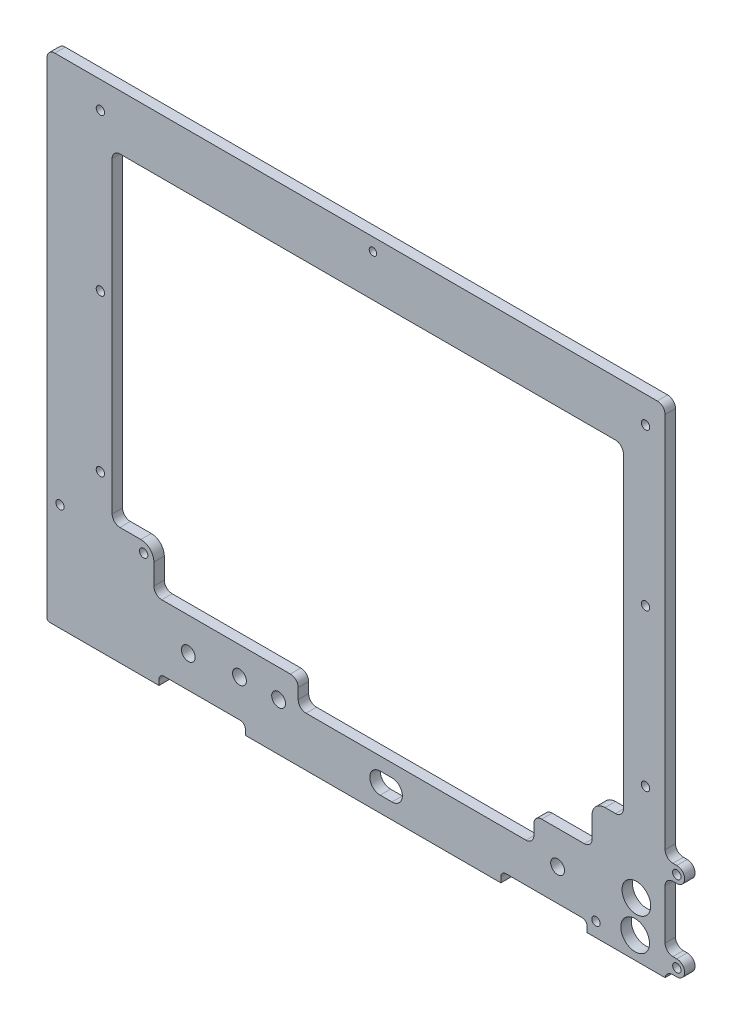
SolidWorks part; units mm, degrees
ref_plane "Plano frontal" through (0, 0, 0) normal (0, 0, 1) x (1, 0, 0)
ref_plane "Plano superior" through (0, 0, 0) normal (0, 1, 0) x (1, 0, 0)
ref_plane "Plano direito" through (0, 0, 0) normal (1, 0, 0) x (0, 0, -1)
sketch "Esboço1" plane through (0, 0, 0) normal (0, 0, 1) x (1, 0, 0)
  line L0 (-36.7564, -93.1156) -> (-55.7564, -93.1156)
  line L1 (-35.7564, -119.1156) -> (124.2436, -119.1156)
  line L2 (-55.7564, -79.1156) -> (-55.7564, 27.8844)
  line L3 (-52.7564, 30.8844) -> (141.2436, 30.8844)
  line L4 (144.2436, -79.1156) -> (144.2436, 27.8844)
  line L5 (168.2436, -138.1156) -> (-79.7564, -138.1156)
  line L6 (169.2436, -137.1156) -> (169.2436, 48.8844)
  line L7 (166.2436, 51.8844) -> (-77.7564, 51.8844)
  line L8 (-80.7564, -137.1156) -> (-80.7564, 48.8844)
  line L9 (44.2436, -142.1156) -> (44.2436, -132.526) construction
  line L10 (144.2436, -93.1156) -> (144.2436, -79.1156)
  line L11 (-36.7564, -93.1156) -> (-36.7564, -118.1156)
  line L12 (125.2436, -93.1156) -> (144.2436, -93.1156)
  line L13 (-36.7564, -93.1156) -> (-41.6564, -93.1156) construction
  line L15 (125.2436, -93.1156) -> (125.2436, -118.1156)
  line L17 (-55.7564, -93.1156) -> (-55.7564, -79.1156)
  arc A2 (141.2436, 30.8844) -> (144.2436, 27.8844) centre (141.2436, 27.8844) cw
  arc A3 (-55.7564, 27.8844) -> (-52.7564, 30.8844) centre (-52.7564, 27.8844) cw
  arc A4 (-77.7564, 51.8844) -> (-80.7564, 48.8844) centre (-77.7564, 48.8844) ccw
  arc A5 (169.2436, 48.8844) -> (166.2436, 51.8844) centre (166.2436, 48.8844) ccw
  arc A6 (-36.7564, -118.1156) -> (-35.7564, -119.1156) centre (-35.7564, -118.1156) ccw
  arc A7 (-79.7564, -138.1156) -> (-80.7564, -137.1156) centre (-79.7564, -137.1156) cw
  arc A9 (168.2436, -138.1156) -> (169.2436, -137.1156) centre (168.2436, -137.1156) ccw
  arc A12 (125.2436, -118.1156) -> (124.2436, -119.1156) centre (124.2436, -118.1156) cw
  dimension "D2" = 1
  dimension "D10" = 44
  dimension "D11" = 3
  dimension "D12" = 45
  dimension "D13" = 1
  dimension "D3" = 250
  dimension "D4" = 190
  dimension "D5" = 21
  dimension "D6" = 19
  dimension "D7" = 25
  dimension "D8" = 25
  dimension "D9" = 45
extrude "Ressalto-extrusão1" add sketch "Esboço1" along normal blind 4
hole_wizard "Furo com folga de M31" positions "Esboço3" profile "Esboço2" hole size "M3" standard "ISO" end condition through all
sketch "Esboço3" plane through (0, 0, 0) normal (0, 0, -1) x (-1, 0, 0)
  line L0 (-44.2436, 30.8844) -> (-44.2436, 180.2437) construction
  line L2 (-148.7436, -78.3479) -> (-148.7436, -20.0979) construction
  line L3 (-148.7436, -20.0979) -> (-148.7436, 41.6521) construction
  line L5 (-144.2436, -93.1156) -> (-144.2436, 27.8844) construction
  line L7 (-141.2436, 30.8844) -> (52.7564, 30.8844) construction
  point P0 (-148.7436, -78.3479)
  point P3 (-148.7436, -18.3479)
  point P6 (-148.7436, 41.6521)
  point P15 (60.2564, 41.6521)
  point P16 (60.2564, -18.3479)
  point P17 (60.2564, -78.3479)
  dimension "D1" = 4.5
sketch "Esboço2" plane through (148.7436, -78.3479, 0) normal (1, 0, 0) x (0, 1, 0)
  line L0 (0, 0) -> (0, 4)
  line L1 (0, 4) -> (1.6, 4)
  line L2 (1.6, 4) -> (1.6, 0)
  line L5 (1.6, 0) -> (0, 0)
  line L11 (0, -6.35) -> (0, 107.95) construction
  dimension "Thru Hole Dia." = 3.2
  dimension "Thru Hole Depth" = 4
sketch "Esboço7" plane through (0, 0, 0) normal (0, 0, -1) x (-1, 0, 0)
  line L0 (-44.2436, 51.8844) -> (-44.2436, 30.8844) construction
  line L1 (-166.2436, 51.8844) -> (77.7564, 51.8844) construction
  line L2 (-141.2436, 30.8844) -> (52.7564, 30.8844) construction
  line L6 (-96.2362, 29.1636) -> (-9.6626, 29.1636)
  spline S0 degree 3 poles (-10.6321, 38.8243) (-13.3611, 39.7077) (-16.8611, 41.895) (-23.764, 41.5879) (-28.2888, 38.1143) (-35.387, 38.3371) (-40.2923, 41.8976) (-47.561, 41.6218) (-51.8021, 38.2519) (-58.7679, 38.1811) (-63.7734, 41.7729) (-71.0378, 41.777) (-75.4011, 38.1925) (-83.1606, 38.2557) (-85.9334, 39.8502) (-91.4032, 41.7449) knots 0.084363 0.084363 0.084363 0.084363 0.13704 0.155895 0.241845 0.26571 0.370676 0.400371 0.532966 0.565247 0.6909 0.722313 0.847966 0.877306 1 1 1 1
  spline S1 degree 3 poles (-91.4032, 41.7449) (-95.9644, 43.3918) (-100.6156, 42.2201) (-102.5051, 40.3958) (-100.6246, 29.1636) (-96.4672, 29.1636) (-96.2362, 29.1636) knots 0 0 0 0 0.37556 0.47556 0.970864 1 1 1 1
  spline S2 degree 3 poles (-10.6321, 38.8243) (-10.3876, 38.7452) (-5.7614, 37.3724) (-7.4535, 29.1636) (-9.6626, 29.1636) knots 0 0 0 0 0.016559 0.331179 0.331179 0.331179 0.331179
extrude "Corte-extrusão2" [suppressed] cut sketch "Esboço7" against normal blind 10
sketch "Esboço8" plane through (0, 0, 4) normal (0, 0, 1) x (1, 0, 0)
  line L0 (-54.6505, 39.2046) -> (19.6639, 39.2046) construction
  text T0 "carbon" font "BankGothic Md BT" height 5
  text T1 "series" font "BankGothic Md BT" height 4
extrude "Corte-extrusão3" [suppressed] cut sketch "Esboço8" against normal blind 10
sketch "Esboço9" [suppressed] plane through (0, 0, 4) normal (0, 0, 1) x (1, 0, 0)
  line L0 (-39.0973, 41.5261) -> (-39.6973, 41.5261)
  line L1 (-45.2993, 42.5543) -> (-46.2117, 40.8118) construction
  line L2 (-44.352, 40.8118) -> (-45.2993, 42.5543) construction
  line L3 (-9.943, 36.8455) -> (-9.9283, 36.2667)
  line L4 (-46.2117, 40.8118) -> (-44.352, 40.8118) construction
  line L5 (-45.2993, 42.5543) -> (-45.5878, 42.0032)
  line L6 (-41.2577, 43.3118) -> (-37.537, 43.3118) construction
  line L7 (-44.967, 41.943) -> (-45.2993, 42.5543)
  line L8 (-45.5878, 40.8118) -> (-44.982, 40.8118)
  line L9 (-39.3353, 40.8118) -> (-40.2755, 40.8118) construction
  line L10 (-44.982, 40.8118) -> (-44.9915, 40.0975)
  line L11 (-45.5878, 40.8118) -> (-45.5878, 40.0975)
  line L12 (-37.6221, 39.2046) -> (-39.3353, 40.8118) construction
  line L13 (-9.3422, 36.8455) -> (-9.324, 35.9885)
  line L14 (-45.5878, 43.3118) -> (-45.5878, 42.0032)
  line L15 (-39.6973, 43.3118) -> (-39.6973, 42.5975)
  line L16 (-33.4773, 43.3118) -> (-33.4773, 42.5975)
  line L17 (-26.4238, 43.3118) -> (-26.4238, 42.5975)
  line L18 (-9.9793, 38.2741) -> (-9.9648, 37.7027)
  line L19 (-44.9488, 43.3118) -> (-44.967, 41.943)
  line L20 (-39.0973, 43.3118) -> (-39.0973, 42.5975)
  line L21 (-32.8773, 43.3118) -> (-32.8773, 42.5975)
  line L22 (-25.8238, 43.3118) -> (-25.8238, 42.5975)
  line L23 (-9.3726, 38.2741) -> (-9.3605, 37.7027)
  line L24 (-35.0077, 43.3118) -> (-31.347, 43.3118) construction
  line L25 (-31.7948, 42.5975) -> (-34.0255, 42.5975) construction
  line L26 (-34.0255, 41.7046) -> (-31.7948, 41.7046) construction
  line L27 (-31.7948, 40.9904) -> (-34.0255, 40.9904) construction
  line L28 (-31.6106, 39.2046) -> (-35.0077, 39.2046) construction
  line L29 (-34.0255, 39.9189) -> (-31.7948, 39.9189) construction
  line L30 (-24.472, 42.5975) -> (-27.7755, 42.5975) construction
  line L31 (-27.71, 43.3118) -> (-24.5375, 43.3118) construction
  line L32 (-27.7755, 39.9189) -> (-24.472, 39.9189) construction
  line L33 (-24.5375, 39.2046) -> (-27.71, 39.2046) construction
  line L34 (-45.5878, 43.3118) -> (-44.9488, 43.3118)
  line L35 (-8.5347, 37.7027) -> (-10.3806, 37.7027) construction
  line L36 (-10.3806, 36.8455) -> (-8.5347, 36.8455) construction
  line L37 (-9.6284, 36.2741) -> (-10.3806, 36.2741) construction
  line L38 (-8.2579, 34.9884) -> (-9.6284, 36.2741) construction
  line L39 (-45.5878, 40.0975) -> (-44.9915, 40.0975)
  line L40 (-26.4238, 39.9189) -> (-26.4238, 39.2046)
  line L41 (-39.6973, 43.3118) -> (-39.0973, 43.3118)
  line L42 (-39.3353, 40.8118) -> (-39.6973, 40.8118)
  line L43 (-37.6221, 39.2046) -> (-39.3353, 40.8118)
  line L44 (-33.4773, 43.3118) -> (-32.8773, 43.3118)
  line L45 (-32.8773, 42.5975) -> (-33.4773, 42.5975)
  line L46 (-33.4773, 41.7046) -> (-32.8773, 41.7046)
  line L47 (-32.8773, 40.9904) -> (-33.4773, 40.9904)
  line L48 (-32.8773, 39.2046) -> (-33.4773, 39.2046)
  line L49 (-33.4773, 39.9189) -> (-32.8773, 39.9189)
  line L50 (-25.8238, 42.5975) -> (-26.4238, 42.5975)
  line L51 (-26.4238, 43.3118) -> (-25.8238, 43.3118)
  line L52 (-26.4238, 39.9189) -> (-25.8238, 39.9189)
  line L53 (-25.8238, 39.2046) -> (-26.4238, 39.2046)
  line L54 (-25.8238, 39.9189) -> (-25.8238, 39.2046)
  line L55 (-9.3605, 37.7027) -> (-9.9648, 37.7027)
  line L56 (-9.943, 36.8455) -> (-9.3422, 36.8455)
  line L57 (-9.6284, 36.2741) -> (-9.9285, 36.2741)
  line L58 (-9.324, 35.9885) -> (-9.6284, 36.2741)
  line L59 (-33.4773, 39.9189) -> (-33.4773, 39.2046)
  line L60 (-32.8773, 39.9189) -> (-32.8773, 39.2046)
  line L61 (-32.8773, 41.7046) -> (-32.8773, 40.9904)
  line L62 (-33.4773, 41.7046) -> (-33.4773, 40.9904)
  line L63 (-44.982, 40.8118) -> (-45.5878, 40.8118)
  line L64 (-40.2755, 41.5261) -> (-37.9681, 41.5261) construction
  line L65 (-39.6973, 42.5975) -> (-39.0973, 42.5975)
  line L66 (-37.9681, 42.5975) -> (-40.2755, 42.5975) construction
  line L67 (-39.6973, 41.5261) -> (-39.6973, 40.8118)
  line L68 (-39.0973, 41.5261) -> (-39.0973, 40.5886)
  line L69 (-9.9793, 38.2741) -> (-9.3726, 38.2741)
  line L70 (-45.7248, 43.3118) -> (-44.7747, 43.3118) construction
  line L71 (-43.9502, 40.0975) -> (-46.6344, 40.0975) construction
  line L72 (-11.1664, 38.2741) -> (-8.1898, 38.2741) construction
  line L73 (-8.2579, 34.9884) -> (-9.6284, 36.2741) construction
extrude "Ressalto-extrusão2" [suppressed] add sketch "Esboço9" against normal blind 4 contours L34 L14 L5 L7 L19 | L11 L39 L10 L8 | L15 L65 L20 L41 | L68 L0 L67 L42 L43 | L45 L21 L44 L16 | L46 L62 L47 L61 | L60 L49 L59 L48 | L51 L17 L50 L22 | L54 L52 L40 L53 | L58 L13 L56 L3 L57 | L69 L18 L55 L23
fillet "Filete1" radius 3 4 edges at (144.2436, -93.1156, 2) (125.2436, -93.1156, 2) (-55.7564, -93.1156, 2) (-36.7564, -93.1156, 2)
hole_wizard "M3 Clearance Hole1" positions "Esboço11" profile "Esboço10" hole size "M3" standard "ISO" end condition through all
sketch "Esboço11" plane through (0, 0, 0) normal (0, 0, -1) x (-1, 0, 0)
  point P0 (-164.23, -97.103)
  point P12 (43.67, -97.103)
  point P15 (75.7428, -97.103)
sketch "Esboço10" plane through (164.23, -97.103, 0) normal (1, 0, 0) x (0, 1, 0)
  line L0 (0, 0) -> (0, 4)
  line L1 (0, 4) -> (1.6, 4)
  line L2 (1.6, 4) -> (1.6, 0)
  line L5 (1.6, 0) -> (0, 0)
  line L11 (0, -6.35) -> (0, 107.95) construction
  dimension "Thru Hole Dia." = 3.2
  dimension "Thru Hole Depth" = 4
sketch "Esboço12" plane through (0, 0, 4) normal (0, 0, 1) x (1, 0, 0)
  line L0 (-56.3564, -95.7372) -> (-56.3564, -98.6056) construction
  line L1 (-55.3564, -95.7372) -> (-55.3564, -98.6056)
  line L2 (-57.3564, -95.7372) -> (-57.3564, -98.6056)
  line L3 (-63.0564, -95.7372) -> (-63.0564, -98.6056) construction
  line L4 (-64.0564, -95.7372) -> (-64.0564, -98.6056)
  line L5 (-62.0564, -95.7372) -> (-62.0564, -98.6056)
  line L6 (-59.7064, -100.1156) -> (-59.7064, -95.2182) construction
  line L7 (-59.7064, -100.1156) -> (-59.7064, -90.1952) construction
  line L8 (-56.3564, -97.1714) -> (-63.0564, -97.1714) construction
  arc A0 (-55.3564, -95.7372) -> (-57.3564, -95.7372) centre (-56.3564, -95.7372) ccw
  arc A1 (-57.3564, -98.6056) -> (-55.3564, -98.6056) centre (-56.3564, -98.6056) ccw
  arc A2 (-64.0564, -95.7372) -> (-62.0564, -95.7372) centre (-63.0564, -95.7372) cw
  arc A3 (-62.0564, -98.6056) -> (-64.0564, -98.6056) centre (-63.0564, -98.6056) cw
  point P2 (-56.3564, -97.1714)
  point P9 (-63.0564, -97.1714)
  dimension "D1" = 1
  dimension "D2" = 6.7
extrude "Corte-extrusão4" [suppressed] cut sketch "Esboço12" against normal blind 10
sketch "Esboço13" plane through (0, 0, 0) normal (0, 0, -1) x (-1, 0, 0)
  line L0 (79.7564, -138.1156) -> (-168.2436, -138.1156) construction
  line L1 (51.3297, -104.4748) -> (68.0831, -104.4748)
  line L2 (51.3297, -104.4748) -> (51.3297, -94.4748)
  line L3 (51.3297, -94.4748) -> (68.0831, -94.4748)
  line L4 (68.0831, -104.4748) -> (68.0831, -94.4748)
  dimension "D1" = 10
  dimension "D2" = 33.6408
extrude "Corte-extrusão5" [suppressed] cut sketch "Esboço13" against normal blind 12
fillet "Filete2" [suppressed] radius 1
sketch "Esboço16" plane through (0, 0, 4) normal (0, 0, 1) x (1, 0, 0)
  line L0 (150.0557, -138.1156) -> (169.2436, -138.1156) construction
  line L3 (-79.7564, -138.1156) -> (168.2436, -138.1156) construction
  line L5 (169.2436, -137.1156) -> (169.2436, 48.8844) construction
  line L6 (169.2436, -127.14) -> (169.2436, -138.1156) construction
hole_wizard "Furo com folga de M32" positions "Esboço19" profile "Esboço18" hole size "M3" standard "Ansi Metric" end condition through all
sketch "Esboço19" plane through (0, 0, 4) normal (0, 0, 1) x (1, 0, 0)
  point P14 (44.2436, 46.9871)
sketch "Esboço18" plane through (44.2436, 46.9871, 4) normal (1, 0, 0) x (0, -1, 0)
  line L0 (0, 0) -> (0, 4)
  line L1 (0, 4) -> (1.435, 4)
  line L2 (1.435, 4) -> (1.435, 0)
  line L5 (1.435, 0) -> (0, 0)
  line L11 (0, -6.35) -> (0, 107.95) construction
  dimension "Thru Hole Dia." = 2.87
  dimension "Thru Hole Depth" = 4
hole_wizard "M3 Clearance Hole2" positions "Sketch2" profile "Sketch1" hole size "M3" standard "ISO" end condition through all
sketch "Sketch2" plane through (0, 0, 4) normal (0, 0, 1) x (1, 0, 0)
  point P0 (161.5603, 35.4802)
  point P3 (161.5603, 4.4802)
sketch "Sketch1" plane through (161.5603, 35.4802, 4) normal (1, 0, 0) x (0, -1, 0)
  line L0 (0, 0) -> (0, 4)
  line L1 (0, 4) -> (1.6, 4)
  line L2 (1.6, 4) -> (1.6, 0)
  line L5 (1.6, 0) -> (0, 0)
  line L11 (0, -6.35) -> (0, 107.95) construction
  dimension "Thru Hole Dia." = 3.2
  dimension "Thru Hole Depth" = 4
sketch "Sketch3" plane through (0, 0, 4) normal (0, 0, 1) x (1, 0, 0)
  line L3 (44.2436, 30.8844) -> (44.2436, 18.6097) construction
  line L8 (141.2436, 30.8844) -> (-52.7564, 30.8844) construction
  line L9 (183.6742, -138.1156) -> (156.2436, -138.1156)
  line L10 (183.6742, 51.8844) -> (183.6742, -138.1156)
  line L11 (156.2436, 51.8844) -> (183.6742, 51.8844)
  line L12 (156.2436, -138.1156) -> (156.2436, 51.8844)
extrude "Cut-Extrude1" cut sketch "Sketch3" against normal blind 10
fillet "Fillet1" [suppressed] radius 3
sketch "Sketch4" [suppressed] plane through (0, 0, 4) normal (0, 0, 1) x (1, 0, 0)
  line L0 (169.2436, -127.14) -> (169.2436, -138.1156) construction
  line L1 (-67.7564, -138.1156) -> (169.2436, -138.1156)
  line L2 (-67.7564, -138.1156) -> (-67.7564, -137.1156)
  line L3 (-67.7564, -137.1156) -> (169.2436, -137.1156)
  line L4 (169.2436, -138.1156) -> (169.2436, -137.1156)
  dimension "D1" = 1
extrude "Cut-Extrude2" [suppressed] cut sketch "Sketch4" against normal blind 10
sketch "Sketch5" plane through (0, 0, 0) normal (0, 0, -1) x (-1, 0, 0)
  line L0 (-44.2436, 30.8844) -> (-44.2436, 20.8984) construction
  line L1 (-141.2436, 30.8844) -> (52.7564, 30.8844) construction
  line L2 (-145.2403, -97.5002) -> (-140.2436, -97.5002)
  line L3 (-145.2403, 30.8844) -> (-145.2403, -97.5002)
  line L4 (-141.2436, 30.8844) -> (52.7564, 30.8844) construction
  line L6 (-137.2442, 30.8844) -> (-145.2403, 30.8844)
  line L10 (-140.2436, 27.9415) -> (-140.2436, -97.5002)
  arc A0 (-137.2442, 30.8844) -> (-140.2436, 27.9415) centre (-137.2442, 27.8844) ccw
  dimension "D1" = 3
extrude "Boss-Extrude1" add sketch "Sketch5" against normal blind 4
sketch "Sketch6" plane through (0, 0, 0) normal (0, 0, -1) x (-1, 0, 0)
  line L1 (-108.9236, -113.1156) -> (-128.2436, -113.1156)
  line L2 (-108.9236, -113.1156) -> (-108.9236, -119.1156)
  line L5 (20.4364, -113.1156) -> (39.7564, -113.1156)
  line L6 (-133.2436, -93.1156) -> (44.7564, -93.1156)
  line L7 (20.4364, -113.1156) -> (20.4364, -119.1156)
  line L13 (39.7564, -96.1156) -> (39.7564, -118.1156)
  line L14 (39.7564, -98.1156) -> (39.7564, -113.1156)
  line L16 (-128.2436, -118.1156) -> (-128.2436, -96.1156)
  line L17 (-128.2436, -113.1156) -> (-128.2436, -98.1156)
  line L21 (35.7564, -119.1156) -> (-124.2436, -119.1156) construction
  line L22 (20.4364, -119.1156) -> (-108.9236, -119.1156)
  arc A0 (39.7564, -98.1156) -> (44.7564, -93.1156) centre (44.7564, -98.1156) cw
  arc A1 (-128.2436, -98.1156) -> (-133.2436, -93.1156) centre (-133.2436, -98.1156) ccw
  dimension "D3" = 5
  dimension "D4" = 5
  dimension "D1" = 3
  dimension "D2" = 3
extrude "Cut-Extrude3" cut sketch "Sketch6" against normal blind 10
fillet "Fillet2" radius 3 3 edges at (-39.7564, -113.1156, 2) (128.2436, -113.1156, 2) (140.2436, -93.1156, 2)
hole_wizard "M3 Clearance Hole3" [suppressed] positions "Sketch8" profile "Sketch7" hole size "M3" standard "ISO"
sketch "Sketch8" plane through (0, 0, 4) normal (0, 0, 1) x (1, 0, 0)
  point P0 (166.0777, -32.1233)
sketch "Sketch7" plane through (166.0777, -32.1233, 4) normal (1, 0, 0) x (0, -1, 0)
  line L0 (0, 0) -> (0, 4)
  line L1 (0, 4) -> (1.7, 4)
  line L2 (1.7, 4) -> (1.7, 0)
  line L5 (1.7, 0) -> (0, 0)
  line L11 (0, -6.35) -> (0, 107.95) construction
  dimension "Thru Hole Dia." = 3.4
  dimension "Thru Hole Depth" = 4
fillet "Fillet3" radius 3 1 edges at (156.2436, 51.8844, 2)
sketch "Sketch9" plane through (0, 0, 0) normal (0, 0, -1) x (-1, 0, 0)
  line L1 (-105.9236, -109.1156) -> (-129.3411, -109.1156)
  line L2 (-105.9236, -109.1156) -> (-105.9236, -119.7288)
  line L3 (-105.9236, -119.7288) -> (-129.3411, -119.7288)
  line L4 (-129.3411, -109.1156) -> (-129.3411, -119.7288)
  line L5 (-15.58, -109.1156) -> (41.1684, -109.1156)
  line L6 (-15.58, -109.1156) -> (-15.58, -119.7288)
  line L7 (-15.58, -119.7288) -> (41.1684, -119.7288)
  line L8 (41.1684, -109.1156) -> (41.1684, -119.7288)
extrude "Boss-Extrude2" add sketch "Sketch9" against normal blind 4
fillet "Fillet4" radius 3 4 edges at (15.58, -119.1156, 2) (15.58, -109.1156, 2) (105.9236, -119.1156, 2) (105.9236, -109.1156, 2)
sketch "Sketch10" plane through (0, 0, 0) normal (0, 0, -1) x (-1, 0, 0)
  line L1 (-156.2436, -135.6156) -> (-160.7436, -135.6156)
  line L2 (-156.2436, -135.6156) -> (-156.2436, -129.6156)
  line L3 (-156.2436, -129.6156) -> (-160.7436, -129.6156)
  line L5 (-156.2436, 48.8844) -> (-156.2436, -138.1156) construction
  line L7 (-156.2436, -98.6156) -> (-160.7436, -98.6156)
  line L8 (-156.2436, -98.6156) -> (-156.2436, -104.6156)
  line L9 (-156.2436, -104.6156) -> (-160.7436, -104.6156)
  arc A0 (-160.7436, -129.6156) -> (-160.7436, -135.6156) centre (-160.7436, -132.6156) ccw
  arc A1 (-160.7436, -98.6156) -> (-160.7436, -104.6156) centre (-160.7436, -101.6156) ccw
extrude "Boss-Extrude3" add sketch "Sketch10" against normal blind 4
hole_wizard "M3 Clearance Hole4" positions "Sketch12" profile "Sketch11" hole size "M3" standard "ISO" end condition through all
sketch "Sketch12" plane through (0, 0, 0) normal (0, 0, -1) x (-1, 0, 0)
  point P0 (-160.7436, -101.6156)
  point P2 (-160.7436, -132.6156)
  point P5 (-129.7436, -132.6156)
sketch "Sketch11" plane through (160.7436, -101.6156, 0) normal (1, 0, 0) x (0, 1, 0)
  line L0 (0, 0) -> (0, 4)
  line L1 (0, 4) -> (1.6, 4)
  line L2 (1.6, 4) -> (1.6, 0)
  line L5 (1.6, 0) -> (0, 0)
  line L11 (0, -6.35) -> (0, 107.95) construction
  dimension "Thru Hole Dia." = 3.2
  dimension "Thru Hole Depth" = 4
fillet "Fillet5" radius 3 4 edges at (156.2436, -135.6156, 2) (156.2436, -129.6156, 2) (156.2436, -98.6156, 2) (156.2436, -104.6156, 2)
hole_wizard "M5 Clearance Hole1" positions "Esboço15" profile "Esboço14" hole size "M5" standard "ISO" end condition through all
sketch "Esboço15" plane through (0, 0, 0) normal (0, 0, -1) x (-1, 0, 0)
  point P1 (-115.0336, -121.8656)
  point P3 (26.5464, -121.8656)
sketch "Esboço14" plane through (115.0336, -121.8656, 0) normal (1, 0, 0) x (0, 1, 0)
  line L0 (0, 0) -> (0, 4)
  line L1 (0, 4) -> (2.65, 4)
  line L2 (2.65, 4) -> (2.65, 0)
  line L5 (2.65, 0) -> (0, 0)
  line L11 (0, -6.35) -> (0, 107.95) construction
  dimension "Thru Hole Dia." = 5.3
  dimension "Thru Hole Depth" = 4
sketch "Sketch13" plane through (0, 0, 4) normal (0, 0, 1) x (1, 0, 0)
  line L0 (-79.7564, -138.1156) -> (156.2436, -138.1156) construction
  line L1 (-4.6702, -138.1156) -> (-37.7877, -138.1156)
  line L2 (-4.6702, -138.1156) -> (-4.6702, -136.0924)
  line L3 (-6.6702, -134.0924) -> (-35.7877, -134.0924)
  line L4 (-37.7877, -138.1156) -> (-37.7877, -136.0924)
  line L5 (126.3985, -138.1156) -> (93.281, -138.1156)
  line L6 (126.3985, -138.1156) -> (126.3985, -136.0924)
  line L7 (124.3985, -134.0924) -> (95.281, -134.0924)
  line L8 (93.281, -138.1156) -> (93.281, -136.0924)
  arc A0 (-35.7877, -134.0924) -> (-37.7877, -136.0924) centre (-35.7877, -136.0924) ccw
  arc A1 (-6.6702, -134.0924) -> (-4.6702, -136.0924) centre (-6.6702, -136.0924) cw
  arc A2 (95.281, -134.0924) -> (93.281, -136.0924) centre (95.281, -136.0924) ccw
  arc A3 (124.3985, -134.0924) -> (126.3985, -136.0924) centre (124.3985, -136.0924) cw
  dimension "D1" = 2
  dimension "D2" = 2
extrude "Cut-Extrude4" cut sketch "Sketch13" against normal through all
sketch "Sketch14" plane through (0, 0, 4) normal (0, 0, 1) x (1, 0, 0)
  line L0 (47.0212, -128.1156) -> (51.5212, -128.1156) construction
  line L1 (47.0212, -124.1156) -> (51.5212, -124.1156)
  line L2 (47.0212, -132.1156) -> (51.5212, -132.1156)
  line L3 (-4.6702, -138.1156) -> (93.281, -138.1156) construction
  arc A0 (47.0212, -124.1156) -> (47.0212, -132.1156) centre (47.0212, -128.1156) ccw
  arc A1 (51.5212, -132.1156) -> (51.5212, -124.1156) centre (51.5212, -128.1156) ccw
  point P2 (49.2712, -128.1156)
  dimension "D1" = 4.5
  dimension "D2" = 4
  dimension "D3" = 10
extrude "Cut-Extrude5" cut sketch "Sketch14" against normal through all
sketch "Sketch15" plane through (0, 0, 0) normal (0, 0, -1) x (-1, 0, 0)
  circle A0 centre (-144.7712, -129.7569) radius 5.5
  circle A1 centre (-145.2436, -117.1156) radius 5.5
  point P0 (-145.2436, -117.1156)
  point P2 (-144.7712, -129.7569)
  point P4 (-145.2436, -117.1156)
  point P5 (-144.7712, -129.7569)
  dimension "D1" = 11
  dimension "D2" = 11
extrude "Cut-Extrude6" cut sketch "Sketch15" against normal through all
hole_wizard "M5 Clearance Hole2" positions "Esboço5" profile "Esboço4" hole size "M5" standard "ISO" end condition through all
sketch "Esboço5" plane through (0, 0, 4) normal (0, 0, 1) x (1, 0, 0)
  line L1 (-6.9364, -119.8706) -> (8.0636, -119.8706)
  line L2 (-6.9364, -119.8706) -> (-6.9364, -138.1156)
  line L3 (-6.9364, -138.1156) -> (8.0636, -138.1156)
  line L4 (8.0636, -119.8706) -> (8.0636, -138.1156)
  line L5 (-79.7564, -138.1156) -> (-37.7877, -138.1156) construction
  point P0 (-6.9364, -119.8706)
  point P3 (-6.9364, -119.8706)
  point P401 (8.0636, -119.8706)
sketch "Esboço4" plane through (-6.9364, -119.8706, 4) normal (1, 0, 0) x (0, -1, 0)
  line L0 (0, 0) -> (0, 4)
  line L1 (0, 4) -> (2.65, 4)
  line L2 (2.65, 4) -> (2.65, 0)
  line L5 (2.65, 0) -> (0, 0)
  line L11 (0, -6.35) -> (0, 107.95) construction
  dimension "Thru Hole Dia." = 5.3
  dimension "Thru Hole Depth" = 4
fillet "Fillet6" radius 3 2 edges at (128.2436, -109.1156, 2) (-39.7564, -109.1156, 2)
